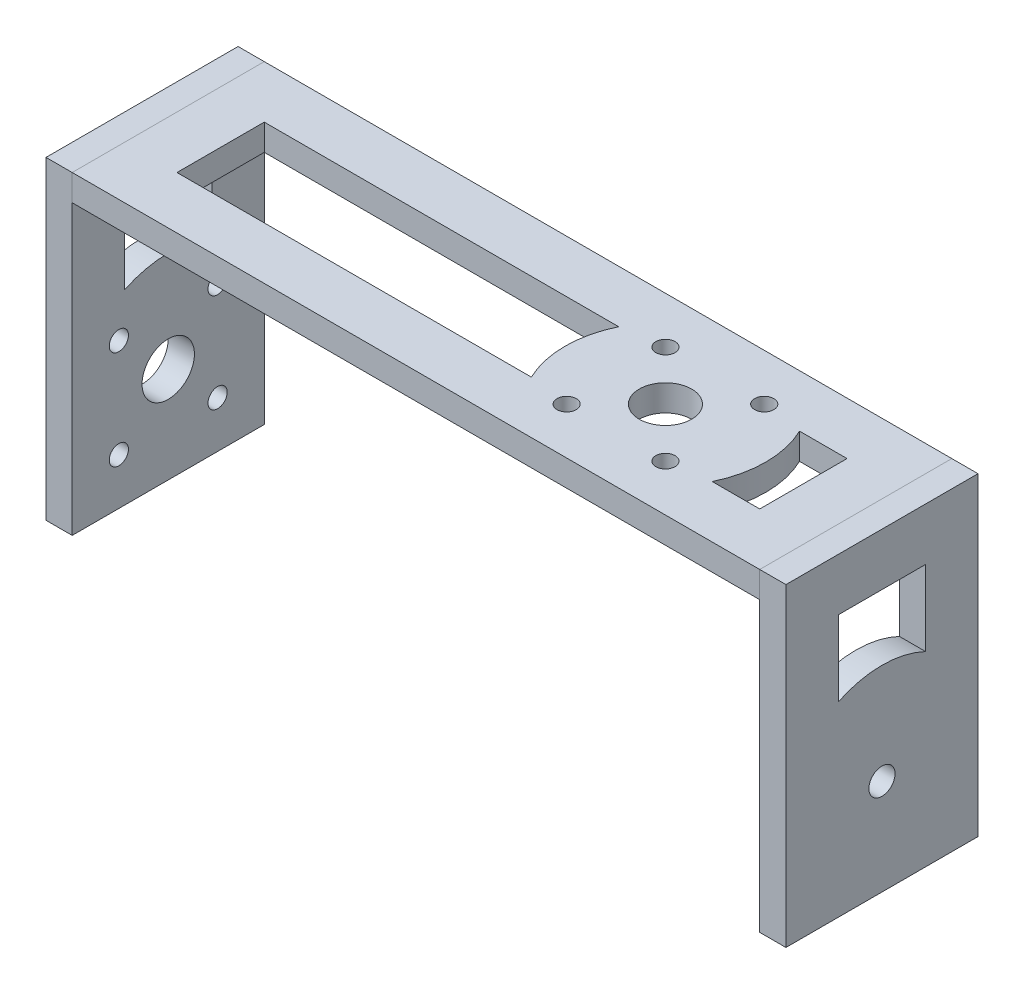
SolidWorks part; units mm, degrees
note: The reader was unsure of these and kept them because the rebuilt part matched: shared geometry of "Sketch1<3>".
ref_plane "Front Plane" through (0, 0, 0) normal (0, 0, 1) x (1, 0, 0)
ref_plane "Top Plane" through (0, 0, 0) normal (0, 1, 0) x (1, 0, 0)
ref_plane "Right Plane" through (0, 0, 0) normal (1, 0, 0) x (0, 0, -1)
sketch "Sketch1" plane through (0, 0, 0) normal (0, 1, 0) x (1, 0, 0)
  line L0 (17.575, 0) -> (19.6963, 2.1213) construction
  line L1 (39.375, 11) -> (-39.375, 11)
  line L2 (39.375, 11) -> (39.375, -11)
  line L3 (39.375, -11) -> (-39.375, -11)
  line L4 (-39.375, 11) -> (-39.375, -11)
  line L5 (39.375, 11) -> (-39.375, -11) construction
  line L6 (39.375, -11) -> (-39.375, 11) construction
  line L7 (-39.375, 11) -> (-42.375, 11)
  line L8 (-39.375, 11) -> (-39.375, -11)
  line L9 (-39.375, -11) -> (-42.375, -11)
  line L10 (-42.375, 11) -> (-42.375, -11)
  line L11 (39.375, 11) -> (42.375, 11)
  line L12 (39.375, 11) -> (39.375, -11)
  line L13 (39.375, -11) -> (42.375, -11)
  line L14 (42.375, 11) -> (42.375, -11)
  line L15 (-33.375, 5) -> (-33.375, 11) construction
  line L16 (33.375, 5) -> (27.9312, 5)
  line L17 (33.375, 5) -> (33.375, -5)
  line L18 (33.375, -5) -> (27.9312, -5)
  line L19 (-33.375, 5) -> (-33.375, -5)
  line L20 (33.375, 5) -> (-33.375, -5) construction
  line L21 (33.375, -5) -> (-33.375, 5) construction
  line L22 (-33.375, 5) -> (-39.375, 5) construction
  line L23 (7.2188, 5) -> (-33.375, 5)
  line L24 (7.2188, -5) -> (-33.375, -5)
  circle A0 centre (17.575, 0) radius 3
  arc A1 (7.2188, 5) -> (7.2188, -5) centre (17.575, 0) ccw
  arc A2 (27.9312, -5) -> (27.9312, 5) centre (17.575, 0) ccw
  point P0 (0, 0)
  point P13 (0, 0)
  dimension "D5" = 6
  dimension "D8" = 23
  dimension "D1" = 78.75
  dimension "D2" = 22
  dimension "D3" = 3
  dimension "D4" = 21.8
  dimension "D6" = 45
  dimension "D7" = 6
extrude "Boss-Extrude1" add sketch "Sketch1" against normal blind 3 contours L1 L4 L3 L2
extrude "Boss-Extrude2" add sketch "Sketch1<3>" against normal blind 36 separate body contours L7 L10 L9 L4 | L14 L11 L2 L13
sketch "Sketch1<3>" plane through (0, 0, 0) normal (0, 1, 0) x (1, 0, 0) same geometry as "Sketch1"
sketch "Sketch2" plane through (-42.375, 0, 0) normal (-1, 0, 0) x (0, 0, 1)
  line L0 (0, -25) -> (5.6569, -19.3431) construction
  line L1 (-11, -36) -> (11, -36) construction
  circle A0 centre (0, -25) radius 3
  circle A1 centre (5.6569, -19.3431) radius 1.1
  dimension "D1" = 6
  dimension "D5" = 2.2
  dimension "D2" = 11
  dimension "D3" = 8
  dimension "D4" = 45
extrude "Cut-Extrude1" cut sketch "Sketch2" against normal up to surface (3 mm away) up to face at (-39.375, -18, 0)
sketch "Sketch3" plane through (42.375, 0, 0) normal (1, 0, 0) x (0, 0, -1)
  circle A0 centre (0, -25) radius 1.5
  dimension "D1" = 3
extrude "Cut-Extrude2" cut sketch "Sketch3" against normal up to surface (3 mm away) up to face at (39.375, -18, 0)
pattern_circular "CirPattern1" count 4 over 360 about axis through (0, -25, 0) along (1, 0, 0) of "Cut-Extrude1"
sketch "Sketch4" plane through (0, 0, 0) normal (0, 1, 0) x (1, 0, 0)
  line L0 (23.2319, 5.6569) -> (17.575, 0) construction
  line L1 (39.375, 11) -> (-39.375, 11) construction
  circle A0 centre (23.2319, 5.6569) radius 1.1
  dimension "D3" = 2.2
  dimension "D1" = 45
  dimension "D2" = 8
extrude "Cut-Extrude3" cut sketch "Sketch4" against normal up to surface (3 mm away) up to face at (17.575, -3, 3)
pattern_circular "CirPattern2" count 4 over 360 about axis through (17.575, 0, 0) along (0, 1, 0) of "Cut-Extrude3"
sketch "Sketch5" plane through (-42.375, 0, 0) normal (-1, 0, 0) x (0, 0, 1)
  line L0 (-11, -6) -> (-5, -6) construction
  line L2 (-5, -14.6438) -> (-5, -6)
  line L3 (-5, -6) -> (5, -6)
  line L4 (5, -14.6438) -> (5, -6)
  line L5 (-11, -36) -> (-11, 0) construction
  line L6 (-5, -6) -> (-5, 0) construction
  line L7 (12.1, 0) -> (-12.1, 0) construction
  line L8 (5, -6) -> (11, -6) construction
  line L9 (11, -36) -> (11, 0) construction
  arc A0 (5, -14.6438) -> (-5, -14.6438) centre (0, -25) ccw
  dimension "D2" = 23
  dimension "D1" = 6
extrude "Cut-Extrude4" cut sketch "Sketch5" against normal up to surface (84.75 mm away) up to face at (42.375, -25, -1.5)
move or copy body "Body-Move/Copy1" bodies to move or copy 111 112 113
